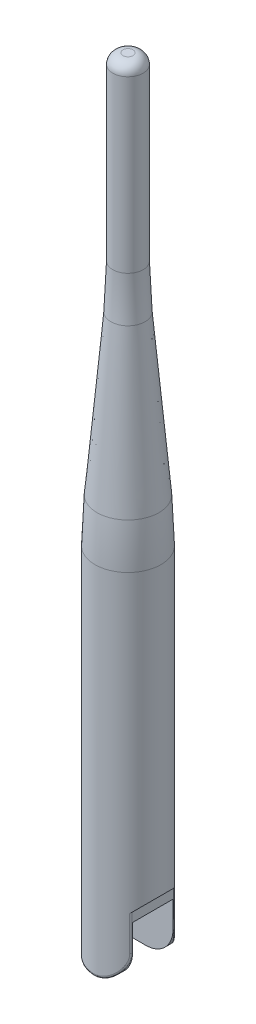
SolidWorks part; units mm, degrees
ref_plane "Front Plane" through (0, 0, 0) normal (0, 0, 1) x (1, 0, 0)
ref_plane "Top Plane" through (0, 0, 0) normal (0, 1, 0) x (1, 0, 0)
ref_plane "Right Plane" through (0, 0, 0) normal (1, 0, 0) x (0, 0, -1)
sketch "Sketch1" plane through (0, 0, 0) normal (0, 0, 1) x (1, 0, 0)
  line L0 (0, 0) -> (0, 166.5303) construction
  line L1 (6.5, 0) -> (6.5, 75)
  line L2 (6.5, 75) -> (3, 115)
  line L3 (3, 115) -> (3, 155)
  line L4 (3, 155) -> (0, 155)
  line L5 (0, 155) -> (0, 0)
  line L6 (0, 0) -> (6.5, 0)
  line L7 (3, 115) -> (0, 115) construction
  line L8 (6.5, 75) -> (0, 75) construction
  dimension "D1" = 13
  dimension "D2" = 6
  dimension "D3" = 75
  dimension "D4" = 40
  dimension "D5" = 40
revolve "Revolve1" add sketch "Sketch1" angle 360 about L0
fillet "Fillet1" radius 2 1 edges at (0, 155, -3)
fillet "Fillet2" radius 100 2 edges at (0, 75, -6.5) (0, 115, -3)
sketch "Sketch2" plane through (0, 0, 0) normal (0, 0, 1) x (1, 0, 0)
  line L0 (6.5, 14) -> (4.9, 12.4)
  line L1 (6.5, 0) -> (6.5, 70.6333) construction
  line L2 (4.9, 12.4) -> (4.9, 5.4)
  line L3 (4.9, 5.4) -> (-0.5, 0) construction
  line L4 (-0.5, 0) -> (6.5, 0)
  line L5 (6.5, 0) -> (6.5, 14)
  line L6 (-6.5, 70.6333) -> (-6.5, 0) construction
  line L7 (-6.5, 0) -> (6.5, 0) construction
  arc A0 (4.9, 5.4) -> (-0.5, 0) centre (-0.5, 5.4) cw
  dimension "D1" = 14
  dimension "D2" = 11.4
  dimension "D3" = 7
extrude "Cut-Extrude1" cut sketch "Sketch2" against normal through all both and the other way through all
ref_plane "Plane1" through (0, 7, 0) normal (0, 1, 0) x (1, 0, 0)
ref_axis "PIVOT" through (0, 7, -7.15) along (0, 0, 1)
sketch "Sketch3" plane through (0, 0, 0) normal (0, 1, 0) x (1, 0, 0)
  line L0 (0, 7.15) -> (0, -7.15) construction
  line L1 (-4.1, -4) -> (6.9, -4)
  line L2 (-4.1, -4) -> (-4.1, 4)
  line L3 (-4.1, 4) -> (6.9, 4)
  line L4 (6.9, -4) -> (6.9, 4)
  circle A0 centre (0, 0) radius 6.5 construction
  point P4 (6.9, 0)
  point P6 (0, -6.5)
  point P7 (6.5, 0)
  point P13 (-6.5, 0)
  point P14 (0, 0)
  dimension "D1" = 8
  dimension "D2" = 2.4
  dimension "D3" = 11
extrude "Cut-Extrude2" cut sketch "Sketch3" along normal blind 10.6
fillet "Fillet3" radius 0.5 5 edges at (4.9, 8.9, 4.2708) (2.7757, 1.107, 5.8775) (4.9, 8.9, -4.2708) (3.6918, 1.9958, -5.3498) (-6.5, 0, 0)
